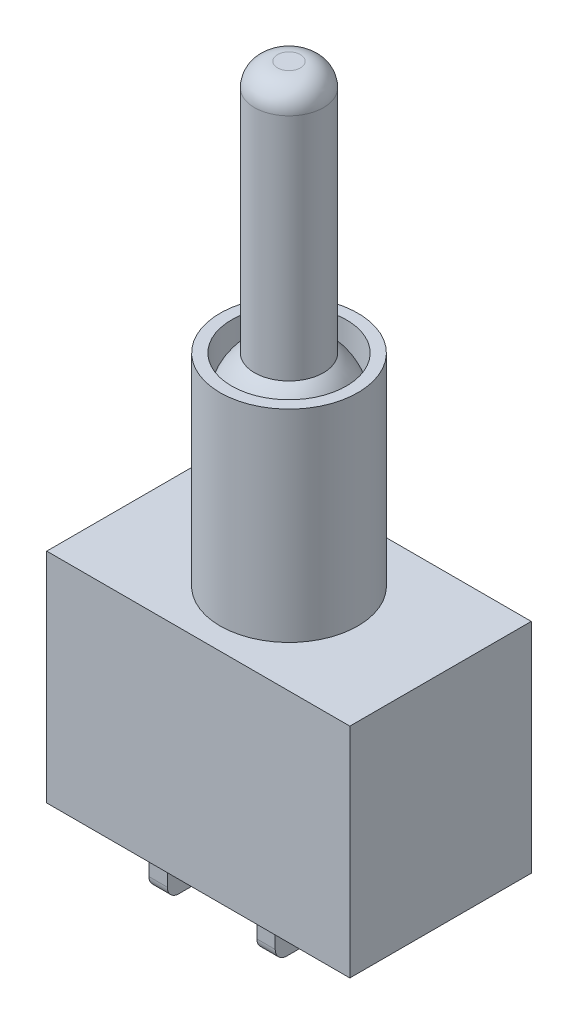
SolidWorks part; units mm, degrees
ref_plane "Спереди" through (0, 0, 0) normal (0, 0, 1) x (1, 0, 0)
ref_plane "Сверху" through (0, 0, 0) normal (0, 1, 0) x (1, 0, 0)
ref_plane "Справа" through (0, 0, 0) normal (1, 0, 0) x (0, 0, -1)
sketch "Sketch1" plane through (0, 0, 0) normal (0, 1, 0) x (1, 0, 0)
  line L1 (6.6, -3.95) -> (-6.6, -3.95)
  line L2 (6.6, -3.95) -> (6.6, 3.95)
  line L3 (6.6, 3.95) -> (-6.6, 3.95)
  line L4 (-6.6, -3.95) -> (-6.6, 3.95)
  line L5 (6.6, -3.95) -> (-6.6, 3.95) construction
  line L6 (6.6, 3.95) -> (-6.6, -3.95) construction
  point P0 (0, 0)
  dimension "D1" = 13.2
  dimension "D2" = 7.9
extrude "Boss-Extrude1" add sketch "Sketch1" along normal blind 9.5
sketch "Sketch2" plane through (0, 9.5, 0) normal (0, 1, 0) x (1, 0, 0)
  line L0 (-6.6, 3.95) -> (6.6, -3.95) construction
  circle A0 centre (0, 0) radius 3
  dimension "D1" = 6
extrude "Boss-Extrude2" add sketch "Sketch2" along normal blind 8.8
sketch "Sketch4" plane through (0, 18.3, 0) normal (0, 1, 0) x (1, 0, 0)
  circle A0 centre (0, 0) radius 2.5
  dimension "D1" = 5
extrude "Cut-Extrude1" cut sketch "Sketch4" against normal blind 2
sketch "Sketch5" plane through (0, 16.3, 0) normal (0, 1, 0) x (1, 0, 0)
  circle A0 centre (0, 0) radius 1.5
  dimension "D1" = 3
extrude "Boss-Extrude3" add sketch "Sketch5" along normal blind 13
sketch "Sketch3" plane through (0, 16.3, 0) normal (0, 1, 0) x (1, 0, 0)
  line L0 (0, -3) -> (0, 3) construction
  line L1 (0, -2.5) -> (0, 2.5)
  circle A0 centre (0, 0) radius 3 construction
  arc A1 (0, -2.5) -> (0, 2.5) centre (0, 0) cw
  point P7 (0, 0)
  dimension "D1" = 5
revolve "Revolve2" add sketch "Sketch3" angle 180 about L0
fillet "Fillet1" radius 1 1 edges at (0, 29.3, 1.5)
sketch "Sketch6" plane through (0, 0, 0) normal (0, -1, 0) x (1, 0, 0)
  line L0 (-4.7, 3.95) -> (-4.7, -3.95) construction
  line L1 (-6.6, 3.95) -> (6.6, 3.95) construction
  line L2 (6.6, -3.95) -> (-6.6, -3.95) construction
  line L3 (0, 3.95) -> (0, -3.95) construction
  line L4 (4.7, 3.95) -> (4.7, -3.95) construction
  line L6 (-6.6, 0) -> (6.6, 0) construction
  line L7 (-4.3, -1) -> (-5.1, -1)
  line L8 (-4.3, -1) -> (-4.3, 1)
  line L9 (-4.3, 1) -> (-5.1, 1)
  line L10 (-5.1, -1) -> (-5.1, 1)
  line L11 (-4.3, -1) -> (-5.1, 1) construction
  line L12 (-4.3, 1) -> (-5.1, -1) construction
  line L13 (-6.6, -3.95) -> (-6.6, 3.95) construction
  line L14 (6.6, 3.95) -> (6.6, -3.95) construction
  line L29 (0.4, -1) -> (-0.4, -1)
  line L30 (0.4, -1) -> (0.4, 1)
  line L31 (0.4, 1) -> (-0.4, 1)
  line L32 (-0.4, -1) -> (-0.4, 1)
  line L33 (0.4, -1) -> (-0.4, 1) construction
  line L34 (0.4, 1) -> (-0.4, -1) construction
  point P10 (0, 0)
  point P11 (-4.7, 0)
  point P23 (0, 0)
  point P37 (0, 0)
  dimension "D1" = 4.7
  dimension "D3" = 2
  dimension "D4" = 0.8
extrude "Boss-Extrude4" add sketch "Sketch6" along normal blind 4
sketch "Sketch7" plane through (-5.1, 0, 0) normal (-1, 0, 0) x (0, 0, 1)
  line L3 (0, -4) -> (0, 0) construction
  line L6 (1, -4) -> (-1, -4) construction
  line L7 (1, 0) -> (-1, 0) construction
  line L15 (0.5, -3.5) -> (-0.5, -3.5)
  line L16 (0.5, -3.5) -> (0.5, -1.5)
  line L17 (0.5, -1.5) -> (-0.5, -1.5)
  line L18 (-0.5, -3.5) -> (-0.5, -1.5)
  line L19 (0.5, -3.5) -> (-0.5, -1.5) construction
  line L20 (0.5, -1.5) -> (-0.5, -3.5) construction
  point P12 (0, 0)
  point P17 (0, -2.5)
  point P28 (0, 0)
  dimension "D1" = 2
  dimension "D2" = 1
extrude "Cut-Extrude3" cut sketch "Sketch7" against normal through all
fillet "Fillet3" radius 0.5 12 edges at (0, -4, 1) (0, -4, -1) (-4.7, -4, -1) (-4.7, -4, 1) (0, -3.5, -0.5) (0, -1.5, -0.5) (0, -3.5, 0.5) (0, -1.5, 0.5) (-4.7, -1.5, 0.5) (-4.7, -1.5, -0.5) (-4.7, -3.5, 0.5) (-4.7, -3.5, -0.5)
